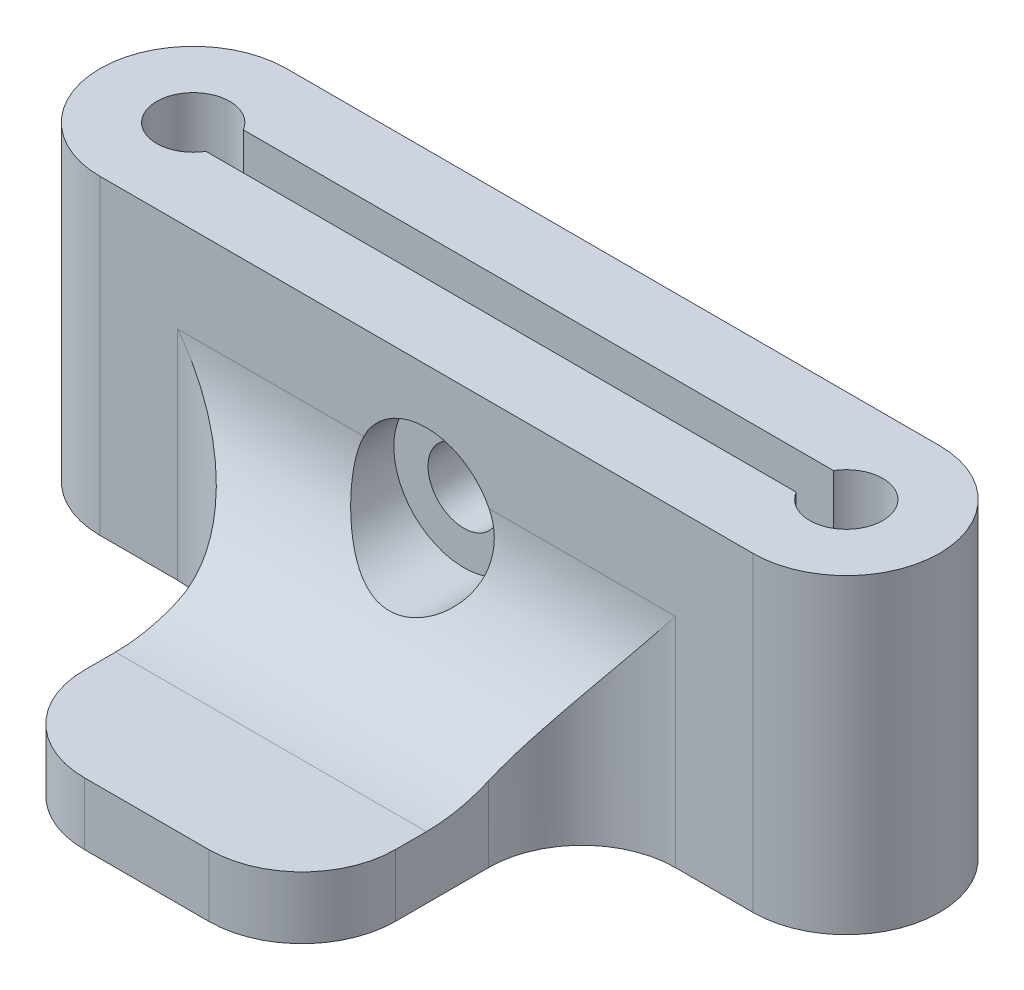
SolidWorks part; units mm, degrees
ref_plane "前视基准面" through (0, 0, 0) normal (0, 0, 1) x (1, 0, 0)
ref_plane "上视基准面" through (0, 0, 0) normal (0, 1, 0) x (1, 0, 0)
ref_plane "右视基准面" through (0, 0, 0) normal (1, 0, 0) x (0, 0, -1)
sketch "草图1" plane through (0, 0, 0) normal (0, 1, 0) x (1, 0, 0)
  line L0 (0, 0) -> (0, 4.7348) construction
  line L1 (0, 0) -> (10.5, 0) construction
  line L2 (-10.5, 0) -> (10.5, 0) construction
  line L3 (-6.4249, 16.8148) -> (6.4249, 16.8148) construction
  line L4 (-6.4249, 16.8148) -> (-6.4249, 3) construction
  line L5 (-6.4249, 3) -> (6.4249, 3) construction
  line L6 (6.4249, 16.8148) -> (6.4249, 3) construction
  line L7 (-6.4249, 16.8148) -> (6.4249, 3) construction
  line L8 (-6.4249, 3) -> (6.4249, 16.8148) construction
  line L9 (-10.5, 3) -> (10.5, 3)
  line L10 (-10.5, -3) -> (10.5, -3)
  circle A0 centre (0, 0) radius 13.5 construction
  circle A1 centre (10.5, 0) radius 1.175
  circle A2 centre (-10.5, 0) radius 1.175
  arc A3 (-10.5, 3) -> (-10.5, -3) centre (-10.5, 0) ccw
  arc A4 (10.5, -3) -> (10.5, 3) centre (10.5, 0) ccw
  point P8 (0, 9.9074)
  point P13 (0, 0)
  dimension "D1" = 27
  dimension "D3" = 2.35
  dimension "D2" = 21
  dimension "D4" = 3
extrude "凸台-拉伸1" add sketch "草图1" along normal blind 10
sketch "草图3" plane through (0, 0, 0) normal (0, -1, 0) x (1, 0, 0)
  line L0 (0, 0) -> (0, 4.5) construction
  line L1 (10.5, -3) -> (-10.5, -3) construction
  line L2 (-5, 12) -> (5, 12)
  line L3 (-5, 12) -> (-5, -3)
  line L4 (-5, -3) -> (5, -3)
  line L5 (5, 12) -> (5, -3)
  line L6 (-5, 12) -> (5, -3) construction
  line L7 (-5, -3) -> (5, 12) construction
  dimension "D1" = 10
  dimension "D2" = 15
extrude "凸台-拉伸2" add sketch "草图3" against normal blind 2
chamfer "倒角2" [suppressed] distance 10 angle 45
fillet "圆角2" radius 3 4 edges at (-5, 1, 12) (5, 1, 12) (5, 1, 3) (-5, 1, 3)
fillet "圆角3" radius 5 1 edges at (0, 2, 3)
sketch "草图4" plane through (0, 0, 0) normal (0, -1, 0) x (1, 0, 0)
  line L1 (-9.4897, -0.6) -> (9.4897, -0.6)
  line L2 (-9.4897, -0.6) -> (-9.4897, 0.6)
  line L3 (-9.4897, 0.6) -> (9.4897, 0.6)
  line L4 (9.4897, -0.6) -> (9.4897, 0.6)
  line L5 (-9.4897, -0.6) -> (9.4897, 0.6) construction
  line L6 (-9.4897, 0.6) -> (9.4897, -0.6) construction
  circle A0 centre (10.5, 0) radius 1.175 construction
  point P0 (0, 0)
  dimension "D1" = 1.2
extrude "切除-拉伸2" cut sketch "草图4" against normal through all
sketch "草图6" plane through (0, 0, 3) normal (0, 0, 1) x (1, 0, 0)
  line L0 (0, 0) -> (0, 6) construction
  line L1 (-10.5, 10) -> (10.5, 10) construction
  circle A0 centre (0, 6) radius 2.25
  dimension "D1" = 4.5
  dimension "D2" = 4
extrude "切除-拉伸4" cut sketch "草图6" against normal blind 1.2 and the other way through all
sketch "草图7" plane through (0, 0, 1.8) normal (0, 0, 1) x (1, 0, 0)
  circle A0 centre (0, 6) radius 1.15
  dimension "D1" = 2.3
extrude "切除-拉伸5" cut sketch "草图7" against normal through all
sketch "草图8" plane through (0, 0, -3) normal (0, 0, -1) x (-1, 0, 0)
  line L0 (0, 8.4249) -> (0, 6) construction
  line L1 (0, 8.4249) -> (-2.1, 7.2124)
  line L2 (-2.1, 7.2124) -> (-2.1, 4.7876)
  line L3 (-2.1, 4.7876) -> (0, 3.5751)
  line L4 (0, 3.5751) -> (2.1, 4.7876)
  line L5 (2.1, 4.7876) -> (2.1, 7.2124)
  line L6 (2.1, 7.2124) -> (0, 8.4249)
  circle A0 centre (0, 6) radius 1.15 construction
  circle A1 centre (0, 6) radius 1.15 construction
  circle A2 centre (0, 6) radius 2.1 construction
  dimension "D1" = 4.2
extrude "切除-拉伸6" cut sketch "草图8" against normal blind 1.5
